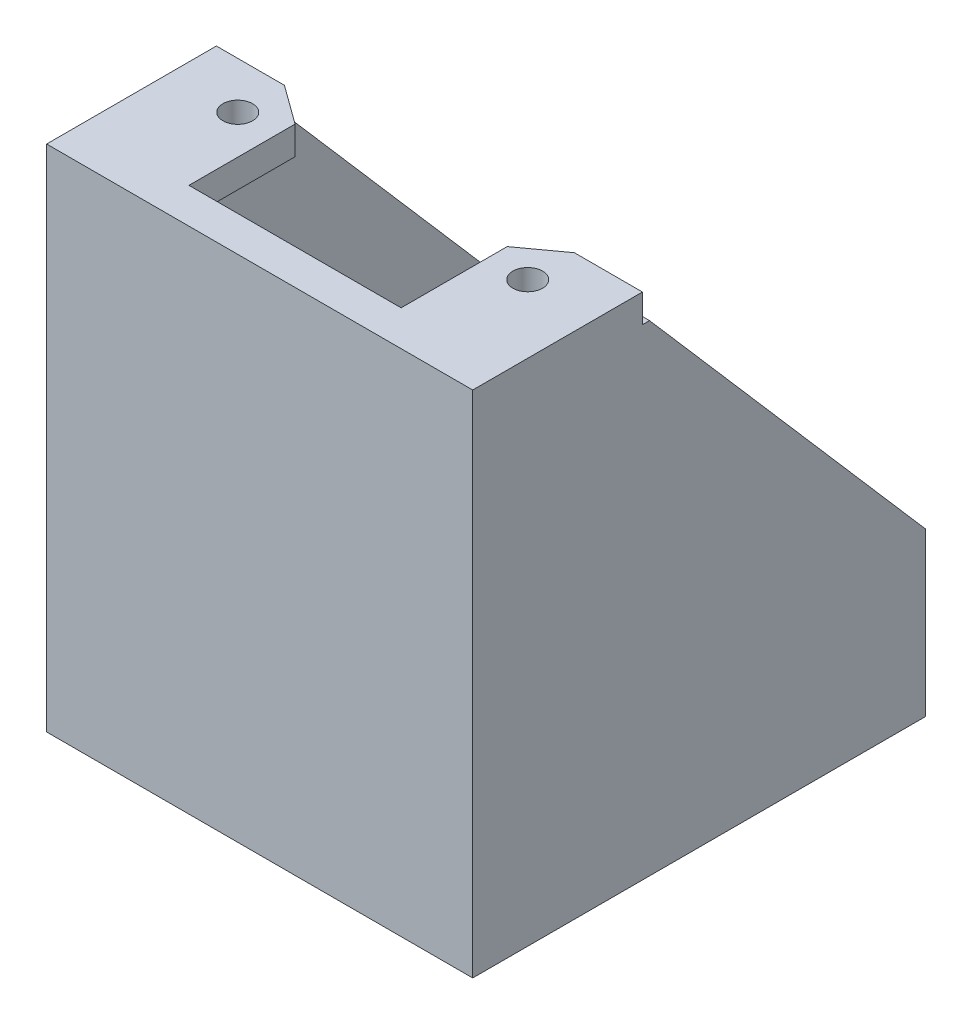
SolidWorks part; units mm, degrees
ref_plane "Front Plane" through (0, 0, 0) normal (0, 0, 1) x (1, 0, 0)
ref_plane "Top Plane" through (0, 0, 0) normal (0, 1, 0) x (1, 0, 0)
ref_plane "Right Plane" through (0, 0, 0) normal (1, 0, 0) x (0, 0, -1)
sketch "Sketch2" plane through (0, 0, 0) normal (0, 1, 0) x (1, 0, 0)
  line L0 (15.061, 0) -> (15.061, 32)
  line L1 (-12.561, 2.5) -> (12.561, 2.5)
  line L2 (-12.561, 2.5) -> (-12.561, 32)
  line L4 (12.561, 2.5) -> (12.561, 32)
  line L5 (15.061, 32) -> (12.561, 32)
  line L7 (-15.061, 32) -> (-15.061, 0)
  line L8 (-15.061, 0) -> (15.061, 0)
  line L10 (-15.061, 32) -> (-12.561, 32)
  point P4 (0, 2.5)
  point P12 (0, 0)
  dimension "D1" = 2.5
  dimension "D2" = 2.5
  dimension "D3" = 29.5
  dimension "D4" = 25.122
extrude "Boss-Extrude1" add sketch "Sketch2" along normal blind 32.5
sketch "Sketch3" plane through (15.061, 0, 0) normal (1, 0, 0) x (0, 0, -1)
  line L0 (32, 10) -> (12.5, 32.5)
  line L3 (12.5, 32.5) -> (32, 32.5)
  line L4 (32, 32.5) -> (32, 10)
  line L5 (0, 16.5671) -> (0, -16.5671) construction
  line L6 (32, 32.5) -> (32, 0) construction
  line L7 (0, 0) -> (32, 0) construction
  line L8 (0, 32.5) -> (32, 32.5) construction
  dimension "D1" = 10
  dimension "D2" = 12.5
extrude "Cut-Extrude1" cut sketch "Sketch3" against normal through all
sketch "Sketch4" plane through (0, 0, 0) normal (0, -1, 0) x (1, 0, 0)
  line L0 (-15.061, 0) -> (-15.061, -32)
  line L2 (-15.061, -32) -> (-10.061, -32)
  line L4 (-7.5, -6) -> (7.5, -6)
  line L6 (10.061, -32) -> (15.061, -32)
  line L8 (15.061, -32) -> (15.061, 0)
  line L9 (15.061, 0) -> (-15.061, 0)
  line L10 (15.061, 0) -> (15.061, -32) construction
  line L13 (-12.561, -2.5) -> (-12.561, -32) construction
  line L18 (-12.561, -10) -> (-7.5, -6)
  line L20 (-12.561, -10) -> (-12.561, -25)
  line L23 (12.561, -32) -> (12.561, -2.5) construction
  line L24 (12.561, -10) -> (12.561, -25)
  line L26 (12.561, -10) -> (7.5, -6)
  line L27 (-10.061, -32) -> (-8.061, -29.4695)
  line L28 (-8.061, -29.4695) -> (-12.561, -25)
  line L29 (10.061, -32) -> (8.061, -29.4695)
  line L31 (8.061, -29.4695) -> (12.561, -25)
  circle A2 centre (-10.2499, -4.95) radius 1.05
  circle A3 centre (-10.2499, -29.4) radius 1.05
  circle A4 centre (10.2499, -29.4) radius 1.05
  circle A5 centre (10.2499, -4.95) radius 1.05
  point P31 (0, -6)
  dimension "D4" = 2
  dimension "D5" = 2.1
  dimension "D10" = 15
  dimension "D11" = 10
  dimension "D2" = 6
  dimension "D3" = 32
  dimension "D6" = 4.8111
  dimension "D7" = 4.95
  dimension "D8" = 4.8111
  dimension "D9" = 29.4
  dimension "D12" = 25
  dimension "D13" = 2
  dimension "D14" = 5
  dimension "D16" = 20.122
extrude "Boss-Extrude2" add sketch "Sketch4" along normal blind 1.5
sketch "Sketch5" plane through (0, 32.5, 0) normal (0, 1, 0) x (1, 0, 0)
  line L10 (-15.061, 12) -> (-10.2499, 12)
  line L11 (-10.2499, 12) -> (-7.5, 10)
  line L12 (-7.5, 10) -> (-7.5, 0)
  line L13 (-15.061, 0) -> (15.061, 0) construction
  line L14 (-7.5, 0) -> (-15.061, 0)
  line L15 (-15.061, 0) -> (-15.061, 12)
  line L16 (15.061, 12) -> (10.2499, 12)
  line L17 (10.2499, 12) -> (7.5, 10)
  line L18 (7.5, 10) -> (7.5, 0)
  line L19 (7.5, 0) -> (15.061, 0)
  line L20 (15.061, 0) -> (15.061, 12)
  circle A0 centre (-10.2499, 4.95) radius 1.05 construction
  circle A1 centre (-10.2499, 8.7) radius 1.05
  circle A2 centre (10.2499, 8.7) radius 1.05
  dimension "D4" = 0
  dimension "D1" = 8.7
  dimension "D2" = 15
  dimension "D3" = 20.4998
  dimension "D5" = 10
  dimension "D6" = 12
extrude "Boss-Extrude3" add sketch "Sketch5" along normal blind 2
fillet "Fillet1" radius 1 2 edges at (8.061, -0.75, -29.4695) (-8.061, -0.75, -29.4695)
sketch "Sketch6" plane through (0, 34.5, 0) normal (0, 1, 0) x (1, 0, 0)
  line L1 (-7.5, 0) -> (7.5, 0)
  line L2 (-7.5, 0) -> (-7.5, 2.5)
  line L3 (-7.5, 2.5) -> (7.5, 2.5)
  line L4 (7.5, 0) -> (7.5, 2.5)
extrude "Boss-Extrude4" add sketch "Sketch6" against normal up to surface (2 mm away) up to face at (-13.811, 32.5, -12.25)
